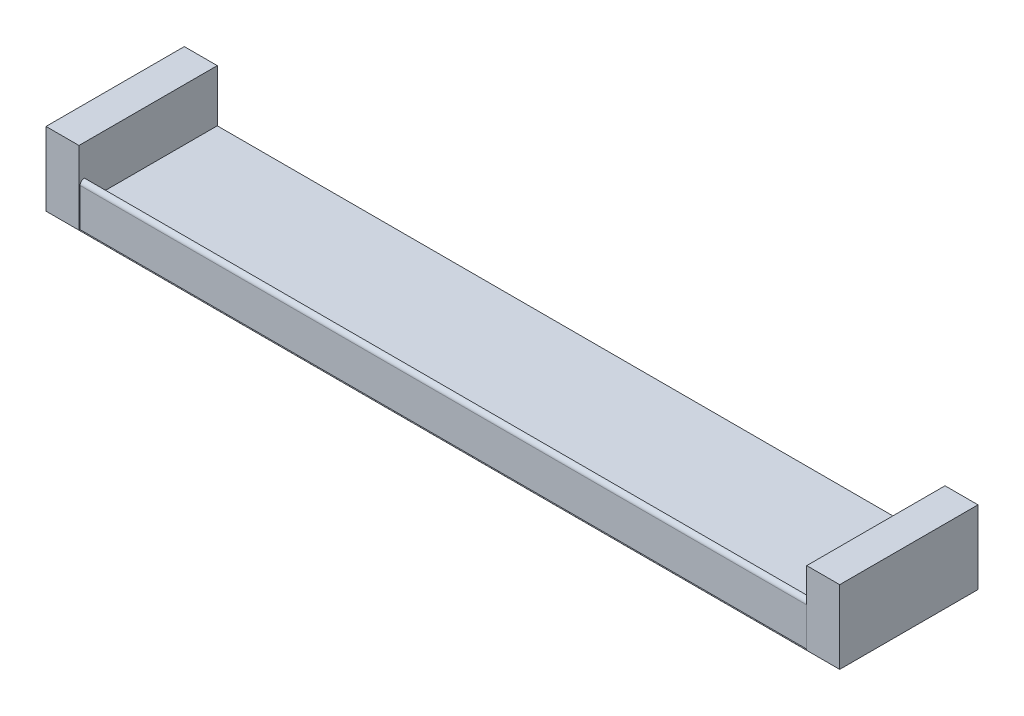
SolidWorks part; units mm, degrees
ref_plane "Alzado" through (0, 0, 0) normal (0, 0, 1) x (1, 0, 0)
ref_plane "Planta" through (0, 0, 0) normal (0, 1, 0) x (1, 0, 0)
ref_plane "Vista lateral" through (0, 0, 0) normal (1, 0, 0) x (0, 0, -1)
sketch "Croquis2" plane through (0, 0, 0) normal (0, 1, 0) x (1, 0, 0)
  line L1 (0, 0) -> (31, 0)
  line L2 (0, 0) -> (0, 130)
  line L3 (0, 130) -> (31, 130)
  line L4 (31, 0) -> (31, 130)
  dimension "D1" = 31
  dimension "D2" = 130
extrude "Saliente-Extruir1" add sketch "Croquis2" along normal blind 69
sketch "Croquis3" plane through (31, 0, 0) normal (1, 0, 0) x (0, 0, -1)
  line L1 (130, 69) -> (130, 0) construction
  line L2 (0, 0) -> (130, 0)
  line L3 (0, 0) -> (0, 40)
  line L4 (0, 40) -> (130, 40)
  line L5 (130, 0) -> (130, 40)
  dimension "D1" = 40
extrude "Saliente-Extruir2" add sketch "Croquis3" along normal blind 715
sketch "Croquis4" plane through (0, 40, 0) normal (0, 1, 0) x (1, 0, 0)
  line L0 (746, 130) -> (31, 130) construction
  line L1 (746, 0) -> (715, 0)
  line L2 (746, 0) -> (746, 130)
  line L3 (746, 130) -> (715, 130)
  line L4 (715, 0) -> (715, 130)
  dimension "D1" = 31
extrude "Saliente-Extruir3" add sketch "Croquis4" along normal blind 29
sketch "Croquis7" plane through (0, 0, -130) normal (0, 0, -1) x (-1, 0, 0)
  line L0 (-715, 40) -> (-31, 40)
  line L1 (-715, 40) -> (-715, 20)
  line L2 (-31, 40) -> (-31, 20)
  line L3 (-715, 20) -> (-31, 20)
  dimension "D1" = 20
extrude "Cortar-Extruir2" cut sketch "Croquis7" against normal blind 125
sketch "Croquis8" plane through (0, 0, 0) normal (0, 0, 1) x (1, 0, 0)
  line L0 (31, 40) -> (715, 40)
  line L1 (31, 40) -> (31, 0.04)
  line L2 (715, 40) -> (715, 0.04)
  line L3 (31, 0.04) -> (715, 0.04)
extrude "Cortar-Extruir3" cut sketch "Croquis8" against normal blind 1
fillet "Redondeo1" radius 4 1 edges at (373, 40, -1)
